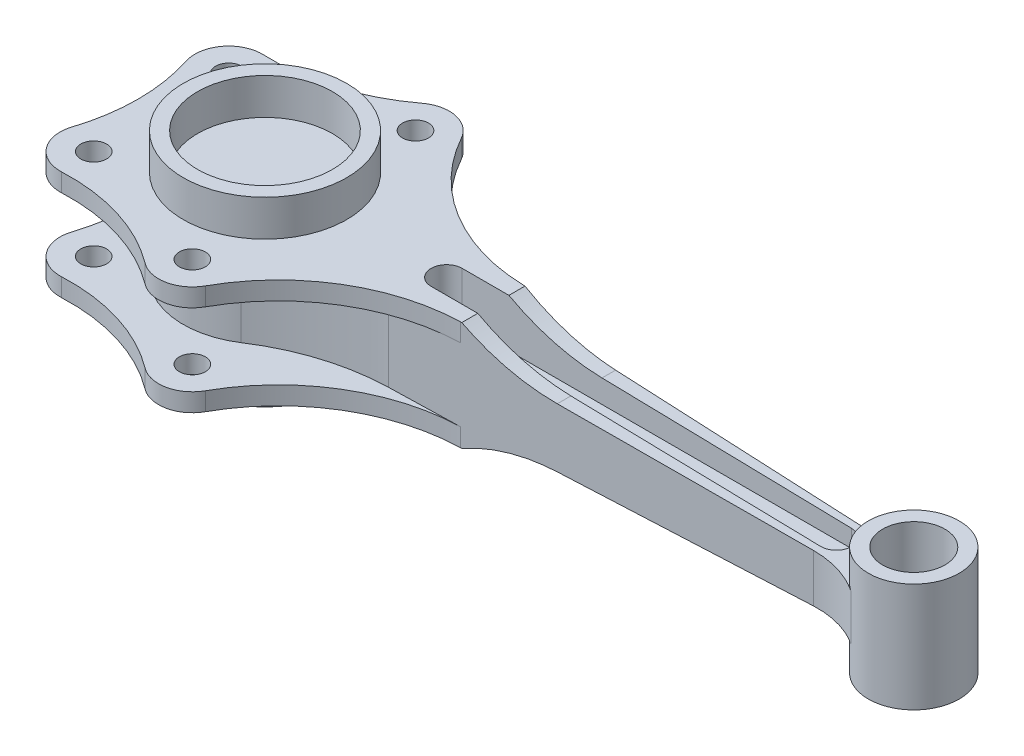
SolidWorks part; units mm, degrees
ref_plane "Front Plane" through (0, 0, 0) normal (0, 0, 1) x (1, 0, 0)
ref_plane "Top Plane" through (0, 0, 0) normal (0, 1, 0) x (1, 0, 0)
ref_plane "Right Plane" through (0, 0, 0) normal (1, 0, 0) x (0, 0, -1)
sketch "Sketch1" plane through (0, 0, 0) normal (0, 1, 0) x (1, 0, 0)
  line L0 (0, 0) -> (250, 0) construction
  line L1 (60.4309, 12.8984) -> (220, 8.7199)
  line L2 (60.4309, -12.8984) -> (220, -8.7199)
  arc A0 (17.2228, 26.3747) -> (17.2228, -26.3747) centre (0, 0) ccw
  arc A1 (240.3054, -14.5693) -> (240.3054, 14.5693) centre (250, 0) ccw
  arc A2 (60.4309, -12.8984) -> (17.2228, -26.3747) centre (62.6036, -95.8699) ccw
  arc A3 (60.4309, 12.8984) -> (17.2228, 26.3747) centre (62.6036, 95.8699) cw
  arc A4 (240.3054, -14.5693) -> (220, -8.7199) centre (220.9162, -43.7079) ccw
  arc A5 (240.3054, 14.5693) -> (220, 8.7199) centre (220.9162, 43.7079) cw
  point P7 (28.3461, -13.7385)
  point P12 (28.3461, 13.7385)
  point P15 (234.6136, -8.3372)
  point P18 (234.6136, 8.3372)
  dimension "D2" = 63
  dimension "D3" = 35
  dimension "D5" = 83
  dimension "D6" = 35
  dimension "D7" = 35
  dimension "D1" = 250
  dimension "D4" = 3
  dimension "D8" = 30
extrude "Boss-Extrude1" add sketch "Sketch1" along normal mid plane 42
sketch "Sketch2" plane through (0, 0, 0) normal (0, 1, 0) x (1, 0, 0)
  circle A0 centre (0, 0) radius 31.5
  circle A1 centre (250, 0) radius 12
  dimension "D1" = 63
  dimension "D2" = 24
extrude "Cut-Extrude1" cut sketch "Sketch2" against normal mid plane 42 contours A1
sketch "Sketch3" plane through (0, -21, 0) normal (0, -1, 0) x (1, 0, 0)
  circle A0 centre (0, 0) radius 26
  dimension "D1" = 52
extrude "Cut-Extrude2" cut sketch "Sketch3" against normal through all
sketch "Sketch4" plane through (0, -21, 0) normal (0, -1, 0) x (1, 0, 0)
  line L0 (0, 0) -> (250, 0) construction
  line L1 (60.4309, 12.8984) -> (220, 8.7199) construction
  line L2 (87.482, 12.19) -> (87.482, -12.19)
  circle A0 centre (15, 43) radius 5
  circle A1 centre (-40, 26) radius 5
  circle A2 centre (15, -43) radius 5
  circle A3 centre (-40, -26) radius 5
  arc A4 (26.3737, 49.2959) -> (7.1819, 53.3864) centre (15, 43) ccw
  arc A5 (-52.3769, 22.0235) -> (-39.4063, 38.9864) centre (-40, 26) cw
  arc A6 (26.3737, -49.2959) -> (7.1819, -53.3864) centre (15, -43) cw
  arc A7 (-52.3769, -22.0235) -> (-39.4063, -38.9864) centre (-40, -26) ccw
  arc A8 (-39.4063, 38.9864) -> (7.1819, 53.3864) centre (-36.118, 110.9113) ccw
  arc A9 (-52.3769, 22.0235) -> (-52.3769, -22.0235) centre (-120.9259, 0) cw
  arc A10 (26.3737, 49.2959) -> (87.482, 12.19) centre (89.3668, 84.1653) ccw
  arc A11 (-39.4063, -38.9864) -> (7.1819, -53.3864) centre (-36.118, -110.9113) cw
  arc A12 (26.3737, -49.2959) -> (87.482, -12.19) centre (89.3668, -84.1653) cw
  dimension "D1" = 10
  dimension "D6" = 13
  dimension "D7" = 72
  dimension "D8" = 72
  dimension "D9" = 72
  dimension "D2" = 26
  dimension "D3" = 40
  dimension "D4" = 43
  dimension "D5" = 15
sketch "Sketch5" plane through (0, 0, 0) normal (0, 1, 0) x (1, 0, 0)
  circle A0 centre (0, 0) radius 31.5
  circle A1 centre (0, 0) radius 26
  dimension "D1" = 63
  dimension "D2" = 52
extrude "Boss-Extrude2" add sketch "Sketch5" along normal mid plane 70
extrude "Boss-Extrude3" add sketch "Sketch4" against normal blind 7
mirror "Mirror1" about plane through (0, 0, 0) normal (0, 1, 0) of "Boss-Extrude3"
sketch "Sketch6" plane through (0, 0, 0) normal (0, 0, 1) x (1, 0, 0)
  line L0 (0, 0) -> (267.5, 0) construction
  line L1 (267.5, -21) -> (267.5, 21) construction
  line L2 (87.482, 21) -> (26.3737, 21) construction
  line L3 (123.8758, 11.3702) -> (232.5, 9)
  line L4 (232.5, 9) -> (232.5, 21)
  line L5 (240.3054, 21) -> (220, 21) construction
  line L6 (88, 21) -> (232.5, 21)
  arc A0 (88, 21) -> (123.8758, 11.3702) centre (125.5773, 89.3516) ccw
  dimension "D1" = 88
  dimension "D2" = 78
  dimension "D3" = 12
  dimension "D4" = 35
  dimension "D5" = 1.25
extrude "Cut-Extrude3" cut sketch "Sketch6" against normal mid plane 40
mirror "Mirror2" about plane through (0, 0, 0) normal (0, 1, 0) of "Cut-Extrude3"
sketch "Sketch7" plane through (0, 21, 0) normal (0, 1, 0) x (1, 0, 0)
  line L0 (232.5, 10.6804) -> (232.5, -10.6804) construction
  line L1 (232.5, 10.6804) -> (232.5, 0)
  arc A0 (240.3054, 14.5693) -> (232.5, 0) centre (250, 0) ccw
  arc A1 (240.3054, -14.5693) -> (240.3054, 14.5693) centre (250, 0) ccw construction
  arc A2 (232.5, 10.6804) -> (240.3054, 14.5693) centre (220.9162, 43.7079) ccw construction
  arc A3 (232.5, 10.6804) -> (240.3054, 14.5693) centre (220.9162, 43.7079) ccw
extrude "Cut-Extrude5" cut sketch "Sketch7" against normal up to surface (12 mm away) up to face at (192.155, 9.8803, 0)
mirror "Mirror10" about plane through (0, 0, 0) normal (0, 0, 1) of "Cut-Extrude5"
sketch "Sketch9" plane through (0, -21, 0) normal (0, -1, 0) x (1, 0, 0)
  line L0 (232.5, -10.6804) -> (232.5, 10.6804) construction
  line L1 (232.5, -10.6804) -> (232.5, 10.6804)
  arc A1 (240.3054, 14.5693) -> (240.3054, -14.5693) centre (250, 0) ccw
  arc A2 (240.3054, -14.5693) -> (232.5, -10.6804) centre (220.9162, -43.7079) ccw construction
  arc A3 (232.5, 10.6804) -> (240.3054, 14.5693) centre (220.9162, 43.7079) ccw construction
  arc A4 (240.3054, -14.5693) -> (232.5, -10.6804) centre (220.9162, -43.7079) ccw
  arc A5 (232.5, 10.6804) -> (240.3054, 14.5693) centre (220.9162, 43.7079) ccw
  line M4 (232.5, 10.6804) -> (232.5, -10.6804)
  arc M5 (232.5, -10.6804) -> (240.3054, -14.5693) centre (220.9162, -43.7079) cw
  arc M7 (240.3054, 14.5693) -> (232.5, 10.6804) centre (220.9162, 43.7079) cw
extrude "Cut-Extrude6" cut sketch "Sketch9" against normal up to surface (12 mm away) contours A1 M7 M4 | A1 L1 M5 region at (234.2034, -21, 9.0393) region at (234.2034, -21, -9.0393) up to face at (192.155, -9.8803, 0)
sketch "Sketch10" plane through (0, 0, 0) normal (0, 1, 0) x (1, 0, 0)
  line L0 (220, 0) -> (70, 0) construction
  line L1 (220, -6) -> (70, -6)
  line L2 (220, 6) -> (70, 6)
  line L3 (250, 0) -> (250, -34.1067) construction
  arc A0 (220, -6) -> (220, 6) centre (220, 0) ccw
  arc A1 (70, 6) -> (70, -6) centre (70, 0) ccw
  point P3 (145, 0)
  dimension "D3" = 6
  dimension "D1" = 150
  dimension "D2" = 30
extrude "Cut-Extrude7" cut sketch "Sketch10" against normal through all from offset 2.5 offset against normal yes
mirror "Mirror11" about plane through (0, 0, 0) normal (0, 1, 0) of "Cut-Extrude7"
